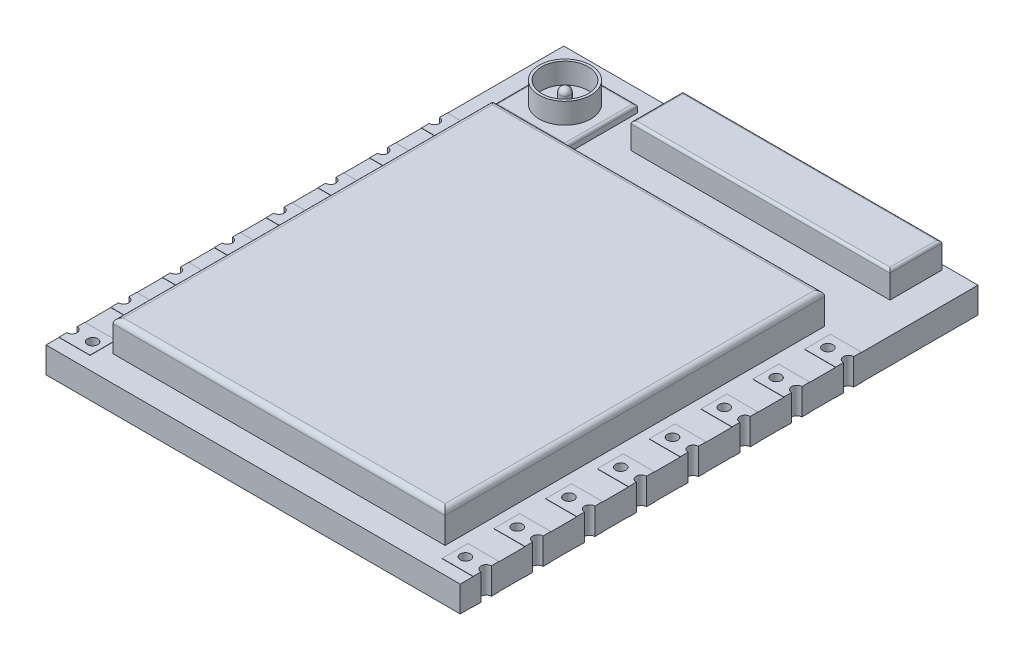
SolidWorks part; units mm, degrees
ref_plane "Front Plane" through (0, 0, 0) normal (0, 0, 1) x (1, 0, 0)
ref_plane "Top Plane" through (0, 0, 0) normal (0, 1, 0) x (1, 0, 0)
ref_plane "Right Plane" through (0, 0, 0) normal (1, 0, 0) x (0, 0, -1)
sketch "Sketch1" plane through (0, 0, 0) normal (0, 1, 0) x (1, 0, 0)
  line L1 (-8, 10) -> (8, 10)
  line L2 (-8, 10) -> (-8, -10)
  line L3 (-8, -10) -> (8, -10)
  line L4 (8, 10) -> (8, -10)
  line L5 (-8, 10) -> (8, -10) construction
  line L6 (-8, -10) -> (8, 10) construction
  point P0 (0, 0)
extrude "Boss-Extrude1" add sketch "Sketch1" along normal blind 1
sketch "Sketch2" plane through (0, 1, 0) normal (0, 1, 0) x (1, 0, 0)
  line L0 (0, 10) -> (0, -10) construction
  line L1 (8, 10) -> (-8, 10) construction
  line L2 (-8, -10) -> (8, -10) construction
  line L3 (-8, 0) -> (8, 0) construction
  line L4 (-8, 10) -> (-8, -10) construction
  line L5 (8, -10) -> (8, 10) construction
  line L6 (6.8, -9) -> (8, -9) construction
  line L7 (8, -9.5) -> (6.8, -9.5)
  line L8 (8, -9.5) -> (8, -9.2)
  line L9 (8, -8.5) -> (6.8, -8.5)
  line L10 (6.8, -9.5) -> (6.8, -8.5)
  line L11 (8, -9) -> (8, -8.5)
  line L12 (8, -7.5) -> (6.8, -7.5)
  line L13 (8, -7.5) -> (8, -7.2)
  line L14 (8, -6.5) -> (6.8, -6.5)
  line L15 (6.8, -7.5) -> (6.8, -6.5)
  line L16 (8, -7) -> (8, -6.5)
  line L17 (6.8, -7) -> (8, -7) construction
  line L18 (8, -5.5) -> (6.8, -5.5)
  line L19 (8, -5.5) -> (8, -5.2)
  line L20 (8, -4.5) -> (6.8, -4.5)
  line L21 (6.8, -5.5) -> (6.8, -4.5)
  line L22 (8, -5) -> (8, -4.5)
  line L23 (6.8, -5) -> (8, -5) construction
  line L24 (8, -3.5) -> (6.8, -3.5)
  line L25 (8, -3.5) -> (8, -3.2)
  line L26 (8, -2.5) -> (6.8, -2.5)
  line L27 (6.8, -3.5) -> (6.8, -2.5)
  line L28 (8, -3) -> (8, -2.5)
  line L29 (6.8, -3) -> (8, -3) construction
  line L30 (8, -1.5) -> (6.8, -1.5)
  line L31 (8, -1.5) -> (8, -1.2)
  line L32 (8, -0.5) -> (6.8, -0.5)
  line L33 (6.8, -1.5) -> (6.8, -0.5)
  line L34 (8, -1) -> (8, -0.5)
  line L35 (6.8, -1) -> (8, -1) construction
  line L36 (8, 0.5) -> (6.8, 0.5)
  line L37 (8, 0.5) -> (8, 0.8)
  line L38 (8, 1.5) -> (6.8, 1.5)
  line L39 (6.8, 0.5) -> (6.8, 1.5)
  line L40 (8, 1) -> (8, 1.5)
  line L41 (6.8, 1) -> (8, 1) construction
  line L42 (8, 2.5) -> (6.8, 2.5)
  line L43 (8, 2.5) -> (8, 2.8)
  line L44 (8, 3.5) -> (6.8, 3.5)
  line L45 (6.8, 2.5) -> (6.8, 3.5)
  line L46 (8, 3) -> (8, 3.5)
  line L47 (6.8, 3) -> (8, 3) construction
  line L48 (8, 4.5) -> (6.8, 4.5)
  line L49 (8, 4.5) -> (8, 4.8)
  line L50 (8, 5.5) -> (6.8, 5.5)
  line L51 (6.8, 4.5) -> (6.8, 5.5)
  line L52 (8, 5) -> (8, 5.5)
  line L53 (6.8, 5) -> (8, 5) construction
  line L54 (-6.8, 5) -> (-8, 5) construction
  line L55 (-6.8, 3) -> (-8, 3) construction
  line L56 (-6.8, 1) -> (-8, 1) construction
  line L57 (-6.8, -1) -> (-8, -1) construction
  line L58 (-6.8, -3) -> (-8, -3) construction
  line L59 (-6.8, -5) -> (-8, -5) construction
  line L60 (-6.8, -7) -> (-8, -7) construction
  line L61 (-6.8, -9) -> (-8, -9) construction
  line L62 (-8, 5) -> (-8, 5.5)
  line L63 (-6.8, 4.5) -> (-6.8, 5.5)
  line L64 (-8, 5.5) -> (-6.8, 5.5)
  line L65 (-8, 4.5) -> (-8, 4.8)
  line L66 (-8, 4.5) -> (-6.8, 4.5)
  line L67 (-8, 3) -> (-8, 3.5)
  line L68 (-6.8, 2.5) -> (-6.8, 3.5)
  line L69 (-8, 3.5) -> (-6.8, 3.5)
  line L70 (-8, 2.5) -> (-8, 2.8)
  line L71 (-8, 2.5) -> (-6.8, 2.5)
  line L72 (-8, 1) -> (-8, 1.5)
  line L73 (-6.8, 0.5) -> (-6.8, 1.5)
  line L74 (-8, 1.5) -> (-6.8, 1.5)
  line L75 (-8, 0.5) -> (-8, 0.8)
  line L76 (-8, 0.5) -> (-6.8, 0.5)
  line L77 (-8, -1) -> (-8, -0.5)
  line L78 (-6.8, -1.5) -> (-6.8, -0.5)
  line L79 (-8, -0.5) -> (-6.8, -0.5)
  line L80 (-8, -1.5) -> (-8, -1.2)
  line L81 (-8, -1.5) -> (-6.8, -1.5)
  line L82 (-8, -3) -> (-8, -2.5)
  line L83 (-6.8, -3.5) -> (-6.8, -2.5)
  line L84 (-8, -2.5) -> (-6.8, -2.5)
  line L85 (-8, -3.5) -> (-8, -3.2)
  line L86 (-8, -3.5) -> (-6.8, -3.5)
  line L87 (-8, -5) -> (-8, -4.5)
  line L88 (-6.8, -5.5) -> (-6.8, -4.5)
  line L89 (-8, -4.5) -> (-6.8, -4.5)
  line L90 (-8, -5.5) -> (-8, -5.2)
  line L91 (-8, -5.5) -> (-6.8, -5.5)
  line L92 (-8, -7) -> (-8, -6.5)
  line L93 (-6.8, -7.5) -> (-6.8, -6.5)
  line L94 (-8, -6.5) -> (-6.8, -6.5)
  line L95 (-8, -7.5) -> (-8, -7.2)
  line L96 (-8, -7.5) -> (-6.8, -7.5)
  line L97 (-8, -9) -> (-8, -8.5)
  line L98 (-6.8, -9.5) -> (-6.8, -8.5)
  line L99 (-8, -8.5) -> (-6.8, -8.5)
  line L100 (-8, -9.5) -> (-8, -9.2)
  line L101 (-8, -9.5) -> (-6.8, -9.5)
  line L102 (8, 5.5) -> (8, -9.5)
  line L103 (-8, -9.5) -> (-8, 5.5)
  circle A0 centre (7.2, -9) radius 0.2
  arc A1 (8, -8.8) -> (8, -9.2) centre (8, -9) ccw
  circle A2 centre (7.2, -7) radius 0.2
  arc A3 (8, -6.8) -> (8, -7.2) centre (8, -7) ccw
  circle A4 centre (7.2, -5) radius 0.2
  arc A5 (8, -4.8) -> (8, -5.2) centre (8, -5) ccw
  circle A6 centre (7.2, -3) radius 0.2
  arc A7 (8, -2.8) -> (8, -3.2) centre (8, -3) ccw
  circle A8 centre (7.2, -1) radius 0.2
  arc A9 (8, -0.8) -> (8, -1.2) centre (8, -1) ccw
  circle A10 centre (7.2, 1) radius 0.2
  arc A11 (8, 1.2) -> (8, 0.8) centre (8, 1) ccw
  circle A12 centre (7.2, 3) radius 0.2
  arc A13 (8, 3.2) -> (8, 2.8) centre (8, 3) ccw
  circle A14 centre (7.2, 5) radius 0.2
  arc A15 (8, 5.2) -> (8, 4.8) centre (8, 5) ccw
  arc A16 (-8, 5.2) -> (-8, 4.8) centre (-8, 5) cw
  circle A17 centre (-7.2, 5) radius 0.2
  arc A18 (-8, 3.2) -> (-8, 2.8) centre (-8, 3) cw
  circle A19 centre (-7.2, 3) radius 0.2
  arc A20 (-8, 1.2) -> (-8, 0.8) centre (-8, 1) cw
  circle A21 centre (-7.2, 1) radius 0.2
  arc A22 (-8, -0.8) -> (-8, -1.2) centre (-8, -1) cw
  circle A23 centre (-7.2, -1) radius 0.2
  arc A24 (-8, -2.8) -> (-8, -3.2) centre (-8, -3) cw
  circle A25 centre (-7.2, -3) radius 0.2
  arc A26 (-8, -4.8) -> (-8, -5.2) centre (-8, -5) cw
  circle A27 centre (-7.2, -5) radius 0.2
  arc A28 (-8, -6.8) -> (-8, -7.2) centre (-8, -7) cw
  circle A29 centre (-7.2, -7) radius 0.2
  arc A30 (-8, -8.8) -> (-8, -9.2) centre (-8, -9) cw
  circle A31 centre (-7.2, -9) radius 0.2
  line M66 (8, -10) -> (8, 10)
  line M68 (-8, 10) -> (-8, -10)
  dimension "D4" = 0.4
  dimension "D1" = 1
  dimension "D2" = 1.2
  dimension "D3" = 8
  dimension "D5" = 0.4
extrude "Cut-Extrude9" cut sketch "Sketch2" against normal up to next (1 mm away) contours A16 L103 M68 | A17 | A19 | A18 L103 M68 | A21 | A20 L103 M68 | A23 | A22 L103 M68 | A25 | A24 L103 M68 | A27 | A26 L103 M68 | A29 | A28 L103 M68 | A31 | A30 L103 M68 | A1 M66 | A0 | A2 | A3 M66 | A6 | A7 M66 | A5 M66 | A4 | A10 | A11 M66 | A9 M66 | A8 | A14 | A15 M66 | A13 M66 | A12 region at (7.9151, 1, 9) region at (7.9151, 1, 7) region at (7.9151, 1, 5) region at (7.9151, 1, 3) region at (7.9151, 1, 1) region at (7.9151, 1, -1) region at (7.9151, 1, -3) region at (7.9151, 1, -5) region at (-7.9151, 1, -5) region at (-7.9151, 1, -3) region at (-7.9151, 1, -1) region at (-7.9151, 1, 1) region at (-7.9151, 1, 3) region at (-7.9151, 1, 5) region at (-7.9151, 1, 7) region at (-7.9151, 1, 9) region at (7.2, 1, 9) region at (7.2, 1, 7) region at (7.2, 1, 5) region at (7.2, 1, 3) region at (7.2, 1, 1) region at (7.2, 1, -1) region at (7.2, 1, -3) region at (7.2, 1, -5) region at (-7.2, 1, -5) region at (-7.2, 1, -3) region at (-7.2, 1, -1) region at (-7.2, 1, 1) region at (-7.2, 1, 3) region at (-7.2, 1, 5) region at (-7.2, 1, 7) region at (-7.2, 1, 9)
extrude "Boss-Extrude2" add sketch "Sketch2<4>" along normal blind 0.01 and the other way blind 1.01 contours A16 L66 L63 L64 A17 M68 | A18 L71 L68 L69 A19 M68 | A20 L76 L73 L74 A21 M68 | A22 L81 L78 L79 A23 M68 | A24 L86 L83 L84 A25 M68 | A1 L102 L9 L10 L7 A0 M66 | A3 L102 L14 L15 L12 A2 M66 | A5 L102 L20 L21 L18 A4 M66 | A7 L102 L26 L27 L24 A6 M66 | A9 L102 L32 L33 L30 A8 M66 | A11 L102 L38 L39 L36 A10 M66 | A13 L102 L44 L45 L42 A12 M66 | A15 L102 L50 L51 L48 A14 M66 | A26 L91 L88 L89 A27 M68 | A28 L96 L93 L94 A29 M68 | A30 L101 L98 L99 A31 M68 region at (7.4, 1, -4.5156) region at (7.4, 1, -2.5156) region at (7.4, 1, -0.5156) region at (7.4, 1, 1.4844) region at (7.4, 1, 3.4844) region at (7.4, 1, 5.4844) region at (7.4, 1, 7.4844) region at (7.4, 1, 9.4844) region at (-7.4, 1, 8.5156) region at (-7.4, 1, 6.5156) region at (-7.4, 1, 4.5156) region at (-7.4, 1, 2.5156) region at (-7.4, 1, 0.5156) region at (-7.4, 1, -1.4844) region at (-7.4, 1, -3.4844) region at (-7.9844, 1, -5.35)
sketch "Sketch2<4>" plane through (0, 1, 0) normal (0, 1, 0) x (1, 0, 0) same geometry as "Sketch2"
sketch "Sketch3" plane through (0, 1, 0) normal (0, 1, 0) x (1, 0, 0)
  line L0 (8, 5.5) -> (8, 10) construction
  line L1 (-3.2, 9.8) -> (6.8, 9.8)
  line L2 (-3.2, 9.8) -> (-3.2, 7.8)
  line L3 (-3.2, 7.8) -> (6.8, 7.8)
  line L4 (6.8, 9.8) -> (6.8, 7.8)
  line L5 (8, 10) -> (-8, 10) construction
  dimension "D1" = 2
  dimension "D2" = 10
  dimension "D3" = 1.2
  dimension "D4" = 0.2
extrude "Boss-Extrude3" add sketch "Sketch3" along normal blind 1
sketch "Sketch4" plane through (0, 1, 0) normal (0, 1, 0) x (1, 0, 0)
  line L1 (-7.1348, 9.1803) -> (-4.3348, 9.1803)
  line L2 (-7.1348, 9.1803) -> (-7.1348, 6.3803)
  line L3 (-7.1348, 6.3803) -> (-4.3348, 6.3803)
  line L4 (-4.3348, 9.1803) -> (-4.3348, 6.3803)
  dimension "D1" = 2.8
extrude "Boss-Extrude4" add sketch "Sketch4" along normal blind 0.3
fillet "Fillet1" radius 0.1 8 edges at (6.8, 2, -8.8) (1.8, 2, -9.8) (-3.2, 2, -8.8) (1.8, 2, -7.8) (-5.7348, 1.3, -6.3803) (-4.3348, 1.3, -7.7803) (-5.7348, 1.3, -9.1803) (-7.1348, 1.3, -7.7803)
sketch "Sketch5" plane through (0, 1.3, 0) normal (0, 1, 0) x (1, 0, 0)
  circle A0 centre (-5.7348, 7.7803) radius 0.9
  circle A1 centre (-5.7348, 7.7803) radius 1
  dimension "D1" = 1.8
extrude "Boss-Extrude5" add sketch "Sketch5" along normal blind 0.8
sketch "Sketch6" plane through (0, 1.3, 0) normal (0, 1, 0) x (1, 0, 0)
  circle A0 centre (-5.7348, 7.7803) radius 0.2
  dimension "D1" = 0.4
extrude "Boss-Extrude6" add sketch "Sketch6" along normal blind 0.6
fillet "Fillet2" radius 0.2 1 edges at (-5.7348, 1.9, -7.5803)
sketch "Sketch8" plane through (0, 1, 0) normal (0, 1, 0) x (1, 0, 0)
  line L1 (-6.4148, 5.6637) -> (6.4148, 5.6637)
  line L2 (-6.4148, 5.6637) -> (-6.4148, -9)
  line L3 (-6.4148, -9) -> (6.4148, -9)
  line L4 (6.4148, 5.6637) -> (6.4148, -9)
  line L5 (0, 10) -> (0, -9) construction
  line L6 (8, 10) -> (-8, 10) construction
  line L8 (-8, -10) -> (8, -10) construction
  point P11 (0, -9)
  dimension "D1" = 1
extrude "Boss-Extrude7" add sketch "Sketch8" along normal blind 1.2
fillet "Fillet3" radius 0.2 4 edges at (0, 2.2, -5.6637) (6.4148, 2.2, 1.6681) (0, 2.2, 9) (-6.4148, 2.2, 1.6681)
